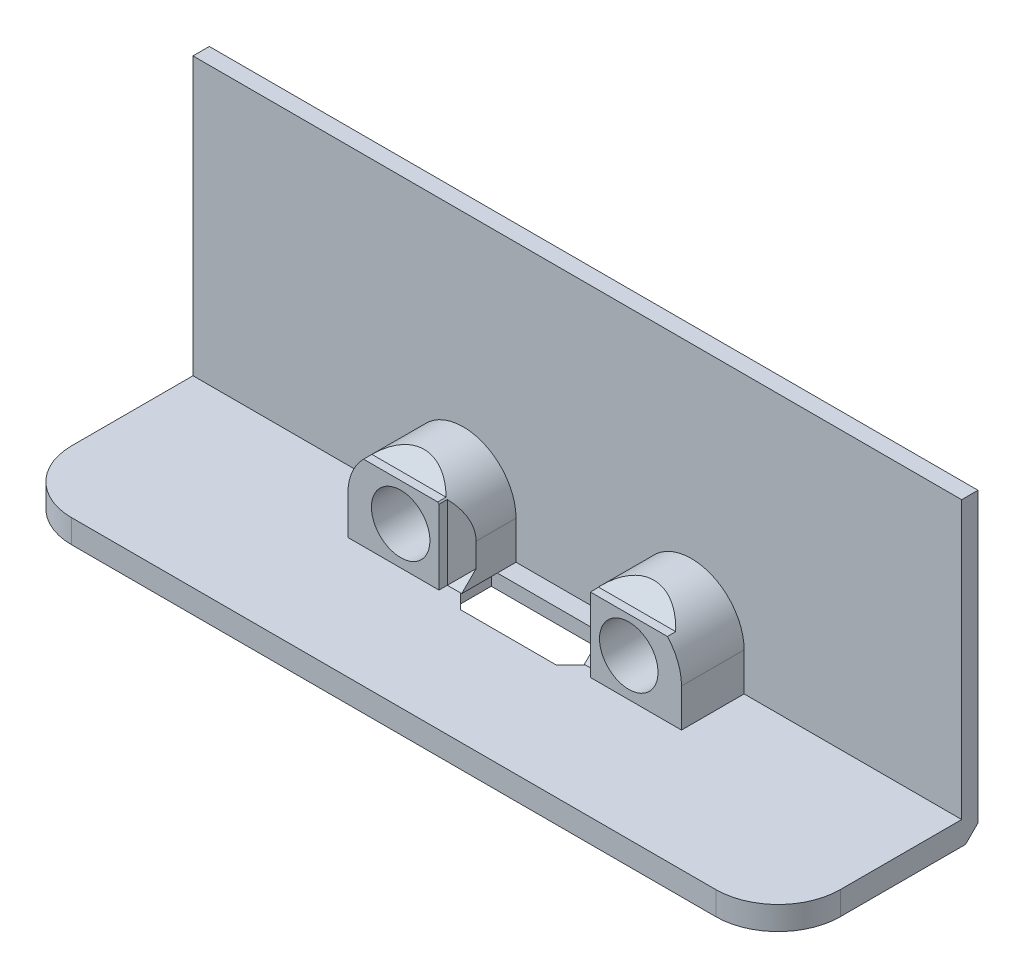
SolidWorks part; units mm, degrees
ref_plane "Front Plane" through (0, 0, 0) normal (0, 0, 1) x (1, 0, 0)
ref_plane "Top Plane" through (0, 0, 0) normal (0, 1, 0) x (1, 0, 0)
ref_plane "Right Plane" through (0, 0, 0) normal (1, 0, 0) x (0, 0, -1)
sketch "Sketch1" plane through (0, 0, 0) normal (0, 0, 1) x (1, 0, 0)
  line L0 (-6.35, 16.9654) -> (-6.35, 17.9654) construction
  line L1 (-23.54, 16.9654) -> (-6.35, 16.9654)
  line L2 (-23.54, 16.9654) -> (-23.54, 0)
  line L3 (-23.54, 0) -> (23.54, 0)
  line L4 (23.54, 16.9654) -> (23.54, 0)
  line L5 (-6.35, 17.9654) -> (6.35, 17.9654) construction
  line L6 (6.35, 17.9654) -> (6.35, 16.9654) construction
  line L7 (6.35, 16.9654) -> (23.54, 16.9654)
  line L9 (23.54, 0) -> (23.54, 18.4194) construction
  line L10 (21.846, 17.2194) -> (23.54, 17.2194) construction
  line L11 (-6.35, 16.9654) -> (6.35, 16.9654)
  dimension "D1" = 1
  dimension "D2" = 0.254
  dimension "D3" = 12.7
extrude "Boss-Extrude1" add sketch "Sketch1" against normal blind 1
sketch "Sketch2" plane through (0, 0, 0) normal (0, -1, 0) x (1, 0, 0)
  line L0 (-23.54, 0) -> (-23.54, -1)
  line L1 (-23.54, -1) -> (23.54, -1)
  line L2 (23.54, -1) -> (23.54, 0)
  line L16 (-23.54, 7.4344) -> (-23.54, 0)
  line L17 (-23.54, 0) -> (-22.1, 0)
  line L18 (-22.1, 0) -> (-22.1, 7.4344)
  line L19 (-19.73, 9.8044) -> (-10.2157, 9.8044)
  line L20 (-10.2157, 9.8044) -> (-10.2157, 5.3594)
  line L21 (-10.2157, 5.3594) -> (-3.7543, 5.3594)
  line L22 (-3.7543, 5.3594) -> (-3.7543, 9.8044)
  line L23 (-3.7543, 9.8044) -> (3.7543, 9.8044)
  line L24 (3.7543, 9.8044) -> (3.7543, 5.3594)
  line L25 (3.7543, 5.3594) -> (10.2157, 5.3594)
  line L26 (10.2157, 5.3594) -> (10.2157, 9.8044)
  line L27 (10.2157, 9.8044) -> (19.73, 9.8044)
  line L28 (22.1, 7.4344) -> (22.1, 0)
  line L29 (22.1, 0) -> (23.54, 0)
  line L30 (23.54, 0) -> (23.54, 7.4344)
  line L31 (19.73, 11.2444) -> (-19.73, 11.2444)
  line L32 (-23.54, 7.4344) -> (-23.54, 0)
  line L46 (23.54, 0) -> (23.54, 7.4344)
  line L47 (19.73, 11.2444) -> (-19.73, 11.2444)
  arc A4 (-19.73, 9.8044) -> (-22.1, 7.4344) centre (-19.73, 7.4344) ccw
  arc A5 (22.1, 7.4344) -> (19.73, 9.8044) centre (19.73, 7.4344) ccw
  arc A6 (23.54, 7.4344) -> (19.73, 11.2444) centre (19.73, 7.4344) ccw
  arc A7 (-19.73, 11.2444) -> (-23.54, 7.4344) centre (-19.73, 7.4344) ccw
  arc A10 (23.54, 7.4344) -> (19.73, 11.2444) centre (19.73, 7.4344) ccw
  arc A11 (-19.73, 11.2444) -> (-23.54, 7.4344) centre (-19.73, 7.4344) ccw
  dimension "D1" = 0
extrude "Boss-Extrude2" add sketch "Sketch2" along normal blind 1.44
sketch "Sketch3" plane through (0, -1.44, 0) normal (0, -1, 0) x (1, 0, 0)
  line L12 (4.1275, 1.143) -> (4.1275, 3.0358)
  line L13 (4.1275, 3.0358) -> (2.9469, 4.2164)
  line L14 (2.9469, 4.2164) -> (-2.9469, 4.2164)
  line L15 (-2.9469, 4.2164) -> (-4.1275, 3.0358)
  line L16 (-4.1275, 3.0358) -> (-4.1275, 1.143)
  line L17 (-4.1275, 1.143) -> (4.1275, 1.143)
  line L18 (4.1275, 1.143) -> (4.1275, 3.0358)
  line L19 (4.1275, 3.0358) -> (2.9469, 4.2164)
  line L20 (2.9469, 4.2164) -> (-2.9469, 4.2164)
  line L21 (-2.9469, 4.2164) -> (-4.1275, 3.0358)
  line L22 (-4.1275, 3.0358) -> (-4.1275, 1.143)
  line L23 (-4.1275, 1.143) -> (4.1275, 1.143)
  dimension "D1" = 0.381
extrude "Cut-Extrude1" cut sketch "Sketch3" against normal through all
sketch "Sketch4" plane through (0, -1.44, 0) normal (0, -1, 0) x (1, 0, 0)
  line L0 (0, -0.381) -> (0, 1.143) construction
  line L1 (5.6515, -0.381) -> (-5.6515, -0.381)
  line L2 (5.6515, -0.381) -> (5.6515, 5.7404)
  line L3 (5.6515, 5.7404) -> (-5.6515, 5.7404)
  line L4 (-5.6515, -0.381) -> (-5.6515, 5.7404)
  line L5 (-4.1275, 1.143) -> (4.1275, 1.143) construction
  line L6 (0, 5.7404) -> (0, 4.2164) construction
  line L7 (2.9469, 4.2164) -> (-2.9469, 4.2164) construction
  line L8 (-5.6515, 2.6797) -> (-4.1275, 2.6797) construction
  line L9 (-4.1275, 3.0358) -> (-4.1275, 1.143) construction
  dimension "D1" = 1.524
  dimension "D2" = 1.524
extrude "Cut-Extrude2" cut sketch "Sketch4" against normal up to surface (0.551 mm away) draft 45
sketch "Sketch5" plane through (0, 0, 0) normal (0, 0, 1) x (1, 0, 0)
  line L15 (10.2157, 0) -> (10.2157, 2.3368)
  line L16 (3.7543, 2.3368) -> (3.7543, 0)
  line L17 (3.7543, 0) -> (10.2157, 0)
  line L18 (10.2157, 0) -> (10.2157, 2.3368)
  line L19 (3.7543, 2.3368) -> (3.7543, 0)
  line L20 (3.7543, 0) -> (10.2157, 0)
  line L21 (-3.7543, 0) -> (-3.7543, 2.3368)
  line L22 (-10.2157, 2.3368) -> (-10.2157, 0)
  line L23 (-10.2157, 0) -> (-3.7543, 0)
  line L24 (-3.7543, 0) -> (-3.7543, 2.3368)
  line L25 (-10.2157, 2.3368) -> (-10.2157, 0)
  line L26 (-10.2157, 0) -> (-3.7543, 0)
  circle A5 centre (6.985, 2.3368) radius 1.7907
  circle A6 centre (6.985, 2.3368) radius 1.7907
  arc A7 (10.2157, 2.3368) -> (3.7543, 2.3368) centre (6.985, 2.3368) ccw
  arc A8 (10.2157, 2.3368) -> (3.7543, 2.3368) centre (6.985, 2.3368) ccw
  circle A9 centre (-6.985, 2.3368) radius 1.7907
  circle A10 centre (-6.985, 2.3368) radius 1.7907
  arc A11 (-3.7543, 2.3368) -> (-10.2157, 2.3368) centre (-6.985, 2.3368) ccw
  arc A12 (-3.7543, 2.3368) -> (-10.2157, 2.3368) centre (-6.985, 2.3368) ccw
  dimension "D1" = 0
  dimension "D2" = 0
  dimension "D3" = 0
  dimension "D4" = 0
extrude "Boss-Extrude3" add sketch "Sketch5" along normal up to surface (3.8354 mm away)
hole_wizard "CSK for #4 Flat Head Machine Screw1" positions "Sketch6" profile "Sketch7" countersink size "#4" standard "ANSI Inch" end condition through all
sketch "Sketch6" plane through (0, 0, -1) normal (0, 0, -1) x (-1, 0, 0)
  point P0 (-6.985, 2.3368)
  point P2 (6.985, 2.3368)
  point P4 (-6.985, 2.3368)
  point P6 (6.985, 2.3368)
  point P8 (-6.985, 2.3368)
  point P10 (6.985, 2.3368)
sketch "Sketch7" plane through (6.985, 2.3368, -1) normal (1, 0, 0) x (0, 1, 0)
  line L0 (0, 0) -> (0, 12.2444)
  line L1 (0, 12.2444) -> (1.6319, 12.2444)
  line L2 (1.6319, 12.2444) -> (1.6319, 1.6638)
  line L3 (1.6319, 1.6638) -> (2.8575, 0.254)
  line L4 (2.8575, 0.254) -> (2.8575, 0)
  line L6 (2.8575, 0) -> (0, 0)
  line L7 (-1.632, 1.6638) -> (-2.8575, 0.254) construction
  line L11 (0, -6.35) -> (0, 107.95) construction
  dimension "Thru Hole Dia." = 3.2639
  dimension "Thru Hole Depth" = 12.2444
  dimension "C'Sink Dia." = 5.715
  dimension "C'Sink Angle" = 82
  dimension "Head Clearance" = 0.254
sketch "Sketch8" plane through (0, 0, 3.8354) normal (0, 0, 1) x (1, 0, 0)
  line L0 (-4.6355, 0) -> (4.6355, 0)
  line L1 (-3.7543, 0) -> (-10.2157, 0) construction
  line L2 (19.73, 0) -> (-19.73, 0) construction
  line L3 (4.6355, 0) -> (4.6355, 4.535)
  line L4 (4.6355, 4.535) -> (11.2525, 4.535)
  line L5 (11.2525, 4.535) -> (11.2525, 13.016)
  line L6 (11.2525, 13.016) -> (-11.8928, 13.016)
  line L7 (-11.8928, 13.016) -> (-11.8928, 4.6351)
  line L8 (-11.8928, 4.6351) -> (-4.6355, 4.6351)
  line L9 (-4.6355, 4.6351) -> (-4.6355, 0)
  line L10 (4.6355, 2.159) -> (4.6355, 0.635) construction
  line L11 (-4.6355, 2.159) -> (-4.6355, 0.635) construction
extrude "Cut-Extrude3" cut sketch "Sketch8" along normal through all and the other way up to surface (2.6924 mm away) draft 45 from offset 0.508 offset against normal yes
chamfer "Chamfer1" distance 0.762 angle 45 1 edges at (0, -1.44, -1)
